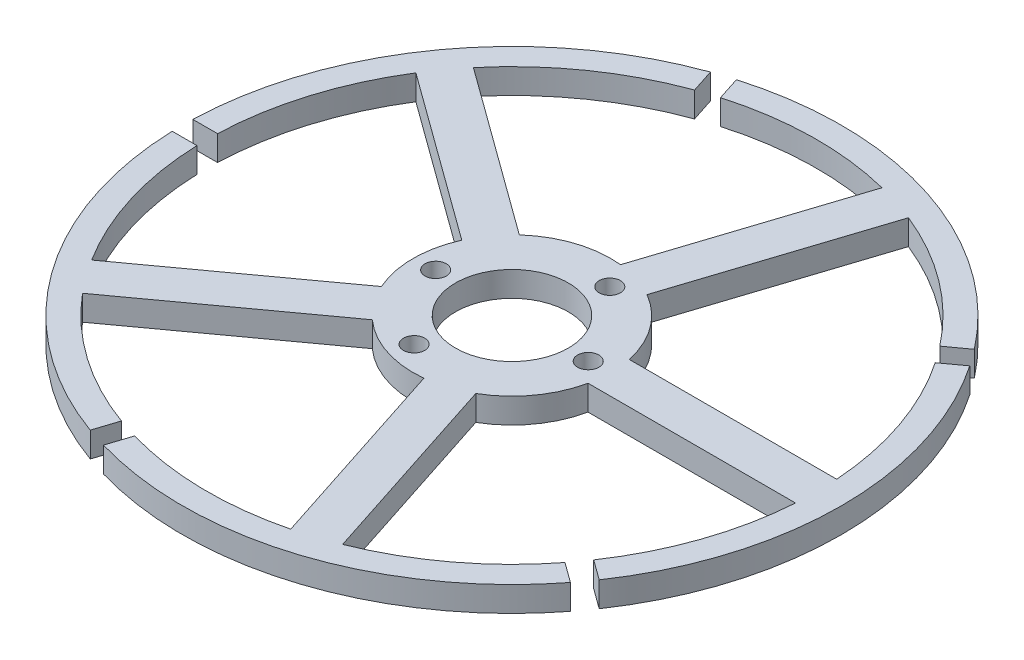
SolidWorks part; units mm, degrees
ref_plane "Front Plane" through (0, 0, 0) normal (0, 0, 1) x (1, 0, 0)
ref_plane "Top Plane" through (0, 0, 0) normal (0, 1, 0) x (1, 0, 0)
ref_plane "Right Plane" through (0, 0, 0) normal (1, 0, 0) x (0, 0, -1)
sketch "Sketch1" plane through (0, 0, 0) normal (0, 1, 0) x (1, 0, 0)
  circle A0 centre (0, 0) radius 20
  dimension "D1" = 40
extrude "Boss-Extrude1" add sketch "Sketch1" along normal blind 1.52 contours A0
sketch "Sketch2" plane through (0, 1.52, 0) normal (0, 1, 0) x (1, 0, 0)
  circle A0 centre (0, 0) radius 18.5
  circle A1 centre (0, 0) radius 6
  dimension "D1" = 12
  dimension "D2" = 37
extrude "Cut-Extrude1" cut sketch "Sketch2" against normal through all
sketch "Sketch3" plane through (0, 1.52, 0) normal (0, 1, 0) x (1, 0, 0)
  circle A0 centre (0, 0) radius 3.425
  dimension "D1" = 6.85
sketch "Sketch10" plane through (0, 0, 0) normal (1, 0, 0) x (0, 0, -1)
  line L0 (0, 0) -> (0, 1.52) construction
  line L1 (3.425, 1.52) -> (-3.425, 1.52) construction
  line L3 (-1.25, 0) -> (1.25, 0)
  line L4 (-1.25, 0) -> (-1.25, 1.52)
  line L5 (-1.25, 1.52) -> (1.25, 1.52)
  line L6 (1.25, 0) -> (1.25, 1.52)
  dimension "D1" = 1.25
  dimension "D2" = 2.5
extrude "Boss-Extrude3" add sketch "Sketch10" along normal up to surface (18.4577 mm away) up to face at (0, 0, 18.5)
pattern_circular "CirPattern1" count 5 over 360 about axis through (0, 1.52, 0) along (0, -1, 0) of "Boss-Extrude3"
extrude "Cut-Extrude3" cut sketch "Sketch3" against normal through all
sketch "Sketch12" plane through (0, 1.52, 0) normal (0, 1, 0) x (1, 0, 0)
  line L0 (16.5398, 11.2443) -> (15.3256, 10.3622)
  line L1 (14.5909, 11.3735) -> (15.3256, 10.3622)
  line L2 (-6.7717, 18.8187) -> (-6.308, 17.3914)
  line L3 (-5.5829, 19.205) -> (-5.1191, 17.7776)
  line L4 (-6.308, 17.3914) -> (-5.1191, 17.7776)
  line L5 (15.8051, 12.2556) -> (14.5909, 11.3735)
  line L6 (15.8051, -12.2556) -> (14.5909, -11.3735)
  line L7 (15.3256, -10.3622) -> (14.5909, -11.3735)
  line L8 (16.5398, -11.2443) -> (15.3256, -10.3622)
  line L9 (-6.7717, -18.8187) -> (-6.308, -17.3914)
  line L10 (-5.1191, -17.7776) -> (-6.308, -17.3914)
  line L11 (-5.5829, -19.205) -> (-5.1191, -17.7776)
  line L12 (-19.9902, 0.625) -> (-18.4894, 0.625)
  line L13 (-18.4894, -0.625) -> (-18.4894, 0.625)
  line L14 (-19.9902, -0.625) -> (-18.4894, -0.625)
  arc A1 (4.5149, 17.9406) -> (-14.1979, 11.8604) centre (0, 0) ccw construction
  circle A2 centre (0, 0) radius 20 construction
  arc A3 (-6.7717, 18.8187) -> (-5.5829, 19.205) centre (0, 0) cw
  arc A4 (15.8051, 12.2556) -> (16.5398, 11.2443) centre (0, 0) cw
  arc A5 (16.5398, -11.2443) -> (15.8051, -12.2556) centre (0, 0) cw
  arc A6 (-5.5829, -19.205) -> (-6.7717, -18.8187) centre (0, 0) cw
  arc A7 (-19.9902, -0.625) -> (-19.9902, 0.625) centre (0, 0) cw
  point P30 (0, 0)
  dimension "D1" = 1.25
  dimension "D2" = 5
extrude "Cut-Extrude8" cut sketch "Sketch12" against normal through all
sketch "Sketch15" plane through (0, 1.52, 0) normal (0, 1, 0) x (1, 0, 0)
  line L0 (6.8926, 17.1681) -> (3.0022, 5.1949) construction
  line L1 (1.8541, 5.7063) -> (1.0584, 3.2574) construction
  line L2 (-1.8541, -5.7063) -> (-1.0584, -3.2574) construction
  line L3 (0, 0) -> (-1.4562, -4.4819) construction
  line L4 (0, 0) -> (-4.7118, 0.0822) construction
  arc A0 (0.6246, 5.9674) -> (3.0022, 5.1949) centre (0, 0) cw construction
  circle A1 centre (0, 0) radius 3.425 construction
  circle A2 centre (1.4562, 4.4819) radius 0.6462
  arc A3 (-4.0129, -4.4606) -> (0.6246, -5.9674) centre (0, 0) ccw construction
  arc A4 (-4.0129, -4.4606) -> (0.6246, -5.9674) centre (0, 0) ccw construction
  circle A5 centre (-1.4562, -4.4819) radius 0.6462
  circle A6 centre (4.7118, -0.0822) radius 0.6462
  circle A7 centre (-4.7118, 0.0822) radius 0.6462
  dimension "D1" = 2
  dimension "D2" = 73
extrude "Cut-Extrude10" cut sketch "Sketch15" against normal through all
